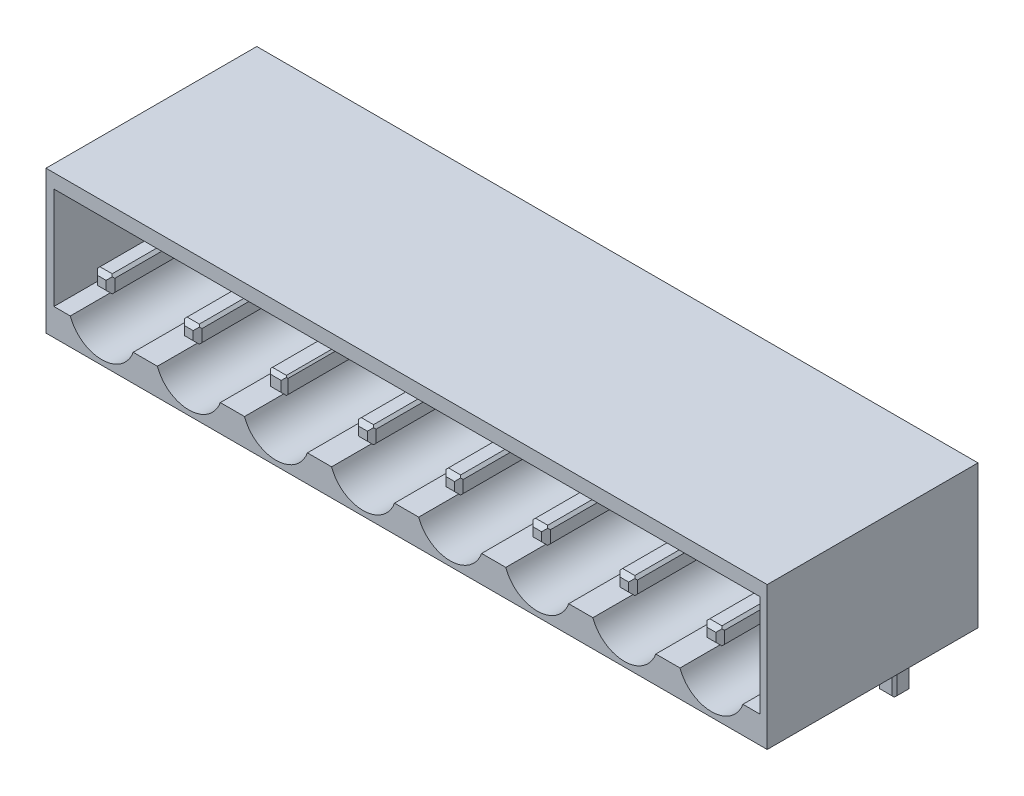
SolidWorks part; units mm, degrees
ref_plane "Спереди" through (0, 0, 0) normal (0, 0, 1) x (1, 0, 0)
ref_plane "Сверху" through (0, 0, 0) normal (0, 1, 0) x (1, 0, 0)
ref_plane "Справа" through (0, 0, 0) normal (1, 0, 0) x (0, 0, -1)
sketch "Эскиз1" plane through (0, 0, 0) normal (0, 0, 1) x (1, 0, 0)
  line L1 (-20.7, 4.1) -> (20.7, 4.1)
  line L2 (-20.7, 4.1) -> (-20.7, -4.1)
  line L3 (-20.7, -4.1) -> (20.7, -4.1)
  line L4 (20.7, 4.1) -> (20.7, -4.1)
  line L5 (-20.7, 4.1) -> (20.7, -4.1) construction
  line L6 (-20.7, -4.1) -> (20.7, 4.1) construction
  point P0 (0, 0)
  dimension "D1" = 8.2
  dimension "D2" = 41.4
extrude "Бобышка-Вытянуть1" add sketch "Эскиз1" along normal blind 12.1
sketch "Эскиз4" plane through (0, 0, 12.1) normal (0, 0, 1) x (1, 0, 0)
  circle A0 centre (-17.5, 0) radius 1.25
  circle A1 centre (-12.5, 0) radius 1.25
  circle A2 centre (-7.5, 0) radius 1.25
  circle A3 centre (-2.5, 0) radius 1.25
  circle A4 centre (2.5, 0) radius 1.25
  circle A5 centre (7.5, 0) radius 1.25
  circle A6 centre (12.5, 0) radius 1.25
  circle A7 centre (17.5, 0) radius 1.25
  dimension "D1" = 2.5
  dimension "D2" = 3.2
  dimension "D3" = 2
  dimension "D4" = 2
  dimension "D5" = 2
  dimension "D6" = 2
  dimension "D7" = 2
extrude "Вырез-Вытянуть3" cut sketch "Эскиз4" against normal blind 8
sketch "Эскиз5" plane through (0, 0, 12.1) normal (0, 0, 1) x (1, 0, 0)
  line L0 (-20.2456, 0) -> (-20.2456, 3.2929)
  line L1 (-20.2456, 3.2929) -> (-9.7215, 3.2929)
  line L4 (-20.2456, -2.549) -> (-20.2456, 0)
  line L5 (-10.6942, -2.549) -> (-9.3058, -2.549)
  line L6 (-19.3058, -2.549) -> (-20.2456, -2.549)
  line L7 (-15.6942, -2.549) -> (-14.3058, -2.549)
  line L11 (-9.7215, 3.2929) -> (-4.7215, 3.2929)
  line L13 (-10.6942, -2.549) -> (-9.3058, -2.549) [skipped]
  line L15 (-4.7215, 3.2929) -> (0.2785, 3.2929)
  line L16 (-5.6942, -2.549) -> (-4.3058, -2.549)
  line L18 (4.3058, -2.549) -> (5.6942, -2.549)
  line L20 (-0.6942, -2.549) -> (0.6942, -2.549)
  line L21 (0.2785, 3.2929) -> (10.2785, 3.2929)
  line L22 (19.3058, -2.549) -> (20.2785, -2.549)
  line L23 (14.3058, -2.549) -> (15.6942, -2.549)
  line L24 (20.2785, 3.2929) -> (20.2785, -2.549)
  line L25 (9.3058, -2.549) -> (10.6942, -2.549)
  line L26 (10.2785, 3.2929) -> (20.2785, 3.2929)
  arc A1 (-9.3058, -2.549) -> (-5.6942, -2.549) centre (-7.5, -1.9) ccw
  arc A2 (-4.3058, -2.549) -> (-0.6942, -2.549) centre (-2.5, -1.9) ccw
  arc A4 (0.6942, -2.549) -> (4.3058, -2.549) centre (2.5, -1.9) ccw
  arc A5 (-19.3058, -2.549) -> (-15.6942, -2.549) centre (-17.5, -1.9) ccw
  arc A6 (-14.3058, -2.549) -> (-10.6942, -2.549) centre (-12.5, -1.9) ccw
  arc A7 (5.6942, -2.549) -> (9.3058, -2.549) centre (7.5, -1.9) ccw
  arc A8 (10.6942, -2.549) -> (14.3058, -2.549) centre (12.5, -1.9) ccw
  arc A9 (15.6942, -2.549) -> (19.3058, -2.549) centre (17.5, -1.9) ccw
  dimension "D1" = 3.2
  dimension "D2" = 2.2
  dimension "D3" = 2
  dimension "D4" = 2
  dimension "D5" = 2
  dimension "D6" = 2
  dimension "D7" = 2
extrude "Вырез-Вытянуть4" cut sketch "Эскиз5" against normal blind 7.8
sketch "Эскиз7" plane through (0, 0, 4.1) normal (0, 0, 1) x (1, 0, 0)
  line L0 (-13, 0.5) -> (-12, 0.5)
  line L1 (-18, 0.5) -> (-17, 0.5)
  line L2 (-18, 0.5) -> (-18, -0.5)
  line L3 (-18, -0.5) -> (-17, -0.5)
  line L4 (-17, 0.5) -> (-17, -0.5)
  line L5 (-18, 0.5) -> (-17, -0.5) construction
  line L6 (-18, -0.5) -> (-17, 0.5) construction
  line L7 (-13, 0.5) -> (-13, -0.5)
  line L8 (-13, -0.5) -> (-12, -0.5)
  line L9 (-12, 0.5) -> (-12, -0.5)
  line L10 (-13, 0.5) -> (-12, -0.5) construction
  line L11 (-13, -0.5) -> (-12, 0.5) construction
  line L12 (-8, 0.5) -> (-7, 0.5)
  line L13 (-8, 0.5) -> (-8, -0.5)
  line L14 (-8, -0.5) -> (-7, -0.5)
  line L15 (-7, 0.5) -> (-7, -0.5)
  line L16 (-8, 0.5) -> (-7, -0.5) construction
  line L17 (-8, -0.5) -> (-7, 0.5) construction
  line L18 (-3, 0.5) -> (-2, 0.5)
  line L19 (-3, 0.5) -> (-3, -0.5)
  line L20 (-3, -0.5) -> (-2, -0.5)
  line L21 (-2, 0.5) -> (-2, -0.5)
  line L22 (-3, 0.5) -> (-2, -0.5) construction
  line L23 (-3, -0.5) -> (-2, 0.5) construction
  line L24 (2, 0.5) -> (3, 0.5)
  line L25 (2, 0.5) -> (2, -0.5)
  line L26 (2, -0.5) -> (3, -0.5)
  line L27 (3, 0.5) -> (3, -0.5)
  line L28 (7, 0.5) -> (8, 0.5)
  line L29 (7, 0.5) -> (7, -0.5)
  line L30 (7, -0.5) -> (8, -0.5)
  line L31 (8, 0.5) -> (8, -0.5)
  line L32 (2, 0.5) -> (3, -0.5) construction
  line L33 (2, -0.5) -> (3, 0.5) construction
  line L34 (7, 0.5) -> (8, -0.5) construction
  line L35 (7, -0.5) -> (8, 0.5) construction
  line L36 (12, 0.5) -> (13, 0.5)
  line L37 (12, 0.5) -> (12, -0.5)
  line L38 (12, -0.5) -> (13, -0.5)
  line L39 (13, 0.5) -> (13, -0.5)
  line L40 (17, 0.5) -> (18, 0.5)
  line L41 (17, 0.5) -> (17, -0.5)
  line L42 (17, -0.5) -> (18, -0.5)
  line L43 (18, 0.5) -> (18, -0.5)
  line L44 (12, 0.5) -> (13, -0.5) construction
  line L45 (12, -0.5) -> (13, 0.5) construction
  line L46 (17, 0.5) -> (18, -0.5) construction
  line L47 (17, -0.5) -> (18, 0.5) construction
  point P0 (-17.5, 0)
  point P7 (-12.5, 0)
  point P12 (-7.5, 0)
  point P17 (-2.5, 0)
  point P22 (12.5, 0)
  point P23 (2.5, 0)
  point P28 (7.5, 0)
  point P37 (17.5, 0)
  dimension "D1" = 1
  dimension "D2" = 1
  dimension "D3" = 2
  dimension "D4" = 2
  dimension "D5" = 2
  dimension "D6" = 2
  dimension "D7" = 2
extrude "Бобышка-Вытянуть2" add sketch "Эскиз7" along normal blind 8
chamfer "Фаска1" distance 0.15 angle 45 24 edges at (-13, -0.5, 8.1) (-13, 0.5, 8.1) (-12, 0.5, 8.1) (-12, -0.5, 8.1) (-17, -0.5, 8.1) (-17, 0.5, 8.1) (-18, -0.5, 8.1) (-18, 0.5, 8.1) (8, -0.5, 8.1) (3, -0.5, 8.1) (8, 0.5, 8.1) (7, -0.5, 8.1) (7, 0.5, 8.1) (3, 0.5, 8.1) (2, -0.5, 8.1) (2, 0.5, 8.1) (13, -0.5, 8.1) (12, -0.5, 8.1) (17, -0.5, 8.1) (17, 0.5, 8.1) (18, 0.5, 8.1) (18, -0.5, 8.1) (13, 0.5, 8.1) (12, 0.5, 8.1)
chamfer "Фаска2" distance 0.25 angle 45 24 edges at (-13, 0, 12.1) (-12.5, 0.5, 12.1) (-12, 0, 12.1) (-12.5, -0.5, 12.1) (-17, 0, 12.1) (-17.5, -0.5, 12.1) (-18, 0, 12.1) (-17.5, 0.5, 12.1) (8, 0, 12.1) (7.5, -0.5, 12.1) (7.5, 0.5, 12.1) (7, 0, 12.1) (3, 0, 12.1) (2.5, -0.5, 12.1) (2, 0, 12.1) (2.5, 0.5, 12.1) (18, 0, 12.1) (17.5, -0.5, 12.1) (17, 0, 12.1) (17.5, 0.5, 12.1) (13, 0, 12.1) (12.5, -0.5, 12.1) (12, 0, 12.1) (12.5, 0.5, 12.1)
sketch "Эскиз8" plane through (0, -4.1, 0) normal (0, -1, 0) x (-1, 0, 0)
  line L0 (13, -2.1) -> (12, -2.1)
  line L1 (18, -2.1) -> (17, -2.1)
  line L2 (18, -2.1) -> (18, -1.1)
  line L3 (18, -1.1) -> (17, -1.1)
  line L4 (17, -2.1) -> (17, -1.1)
  line L5 (18, -2.1) -> (17, -1.1) construction
  line L6 (18, -1.1) -> (17, -2.1) construction
  line L7 (13, -2.1) -> (13, -1.1)
  line L8 (13, -1.1) -> (12, -1.1)
  line L9 (12, -2.1) -> (12, -1.1)
  line L10 (13, -2.1) -> (12, -1.1) construction
  line L11 (13, -1.1) -> (12, -2.1) construction
  line L12 (8, -2.1) -> (7, -2.1)
  line L13 (8, -2.1) -> (8, -1.1)
  line L14 (8, -1.1) -> (7, -1.1)
  line L15 (7, -2.1) -> (7, -1.1)
  line L16 (8, -2.1) -> (7, -1.1) construction
  line L17 (8, -1.1) -> (7, -2.1) construction
  line L18 (3, -2.1) -> (2, -2.1)
  line L19 (3, -2.1) -> (3, -1.1)
  line L20 (3, -1.1) -> (2, -1.1)
  line L21 (2, -2.1) -> (2, -1.1)
  line L22 (3, -2.1) -> (2, -1.1) construction
  line L23 (3, -1.1) -> (2, -2.1) construction
  line L24 (-2, -2.1) -> (-3, -2.1)
  line L25 (-2, -2.1) -> (-2, -1.1)
  line L26 (-2, -1.1) -> (-3, -1.1)
  line L27 (-3, -2.1) -> (-3, -1.1)
  line L28 (-7, -2.1) -> (-8, -2.1)
  line L29 (-7, -2.1) -> (-7, -1.1)
  line L30 (-7, -1.1) -> (-8, -1.1)
  line L31 (-8, -2.1) -> (-8, -1.1)
  line L32 (-2, -2.1) -> (-3, -1.1) construction
  line L33 (-2, -1.1) -> (-3, -2.1) construction
  line L34 (-7, -2.1) -> (-8, -1.1) construction
  line L35 (-7, -1.1) -> (-8, -2.1) construction
  line L36 (-12, -2.1) -> (-13, -2.1)
  line L37 (-12, -2.1) -> (-12, -1.1)
  line L38 (-12, -1.1) -> (-13, -1.1)
  line L39 (-13, -2.1) -> (-13, -1.1)
  line L40 (-17, -2.1) -> (-18, -2.1)
  line L41 (-17, -2.1) -> (-17, -1.1)
  line L42 (-17, -1.1) -> (-18, -1.1)
  line L43 (-18, -2.1) -> (-18, -1.1)
  line L44 (-12, -2.1) -> (-13, -1.1) construction
  line L45 (-12, -1.1) -> (-13, -2.1) construction
  line L46 (-17, -2.1) -> (-18, -1.1) construction
  line L47 (-17, -1.1) -> (-18, -2.1) construction
  point P0 (17.5, -1.6)
  point P7 (12.5, -1.6)
  point P12 (7.5, -1.6)
  point P17 (2.5, -1.6)
  point P22 (-2.5, -1.6)
  point P27 (-7.5, -1.6)
  point P32 (-12.5, -1.6)
  point P37 (-17.5, -1.6)
  dimension "D1" = 1
  dimension "D2" = 1
  dimension "D3" = 3.2
  dimension "D4" = 1.6
  dimension "D5" = 2
  dimension "D6" = 2
  dimension "D7" = 2
  dimension "D8" = 2
  dimension "D9" = 2
extrude "Бобышка-Вытянуть3" add sketch "Эскиз8" along normal blind 4
chamfer "Фаска3" distance 0.15 angle 45 32 edges at (-17, -6.1, 1.1) (-12, -6.1, 1.1) (-18, -6.1, 1.1) (-17, -6.1, 2.1) (-12, -6.1, 2.1) (-13, -6.1, 1.1) (-13, -6.1, 2.1) (-18, -6.1, 2.1) (-2, -0.5, 8.1) (-3, -0.5, 8.1) (-2, 0.5, 8.1) (-3, 0.5, 8.1) (-2, -6.1, 1.1) (-2, -6.1, 2.1) (-3, -6.1, 1.1) (-3, -6.1, 2.1) (3, -6.1, 1.1) (8, -6.1, 1.1) (8, -6.1, 2.1) (7, -6.1, 1.1) (7, -6.1, 2.1) (3, -6.1, 2.1) (2, -6.1, 1.1) (2, -6.1, 2.1) (17, -6.1, 1.1) (13, -6.1, 1.1) (18, -6.1, 1.1) (18, -6.1, 2.1) (13, -6.1, 2.1) (12, -6.1, 1.1) (17, -6.1, 2.1) (12, -6.1, 2.1)
chamfer "Фаска4" distance 0.25 angle 45 32 edges at (-12, -8.1, 1.6) (-13, -8.1, 1.6) (-12.5, -8.1, 2.1) (-12.5, -8.1, 1.1) (-18, -8.1, 1.6) (-17.5, -8.1, 2.1) (-17, -8.1, 1.6) (-17.5, -8.1, 1.1) (-2.5, -8.1, 1.1) (-3, -8.1, 1.6) (-2.5, -8.1, 2.1) (-2, -8.1, 1.6) (-2.5, -0.5, 12.1) (-3, 0, 12.1) (-2, 0, 12.1) (-2.5, 0.5, 12.1) (7, -8.1, 1.6) (7.5, -8.1, 1.1) (8, -8.1, 1.6) (7.5, -8.1, 2.1) (3, -8.1, 1.6) (2.5, -8.1, 1.1) (2, -8.1, 1.6) (2.5, -8.1, 2.1) (18, -8.1, 1.6) (17.5, -8.1, 1.1) (17, -8.1, 1.6) (17.5, -8.1, 2.1) (13, -8.1, 1.6) (12.5, -8.1, 1.1) (12, -8.1, 1.6) (12.5, -8.1, 2.1)
chamfer "Фаска6" distance 0.1 angle 45 4 edges at (-8, -0.5, 8.1) (-7, -0.5, 8.1) (-7, 0.5, 8.1) (-8, 0.5, 8.1)
chamfer "Фаска7" distance 0.2 angle 45 4 edges at (-7, 0, 12.1) (-7.5, -0.5, 12.1) (-8, 0, 12.1) (-7.5, 0.5, 12.1)
chamfer "Фаска8" distance 0.1 angle 45 4 edges at (-8, -6.1, 1.1) (-7, -6.1, 1.1) (-8, -6.1, 2.1) (-7, -6.1, 2.1)
chamfer "Фаска9" distance 0.2 angle 45 4 edges at (-7, -8.1, 1.6) (-7.5, -8.1, 1.1) (-8, -8.1, 1.6) (-7.5, -8.1, 2.1)
